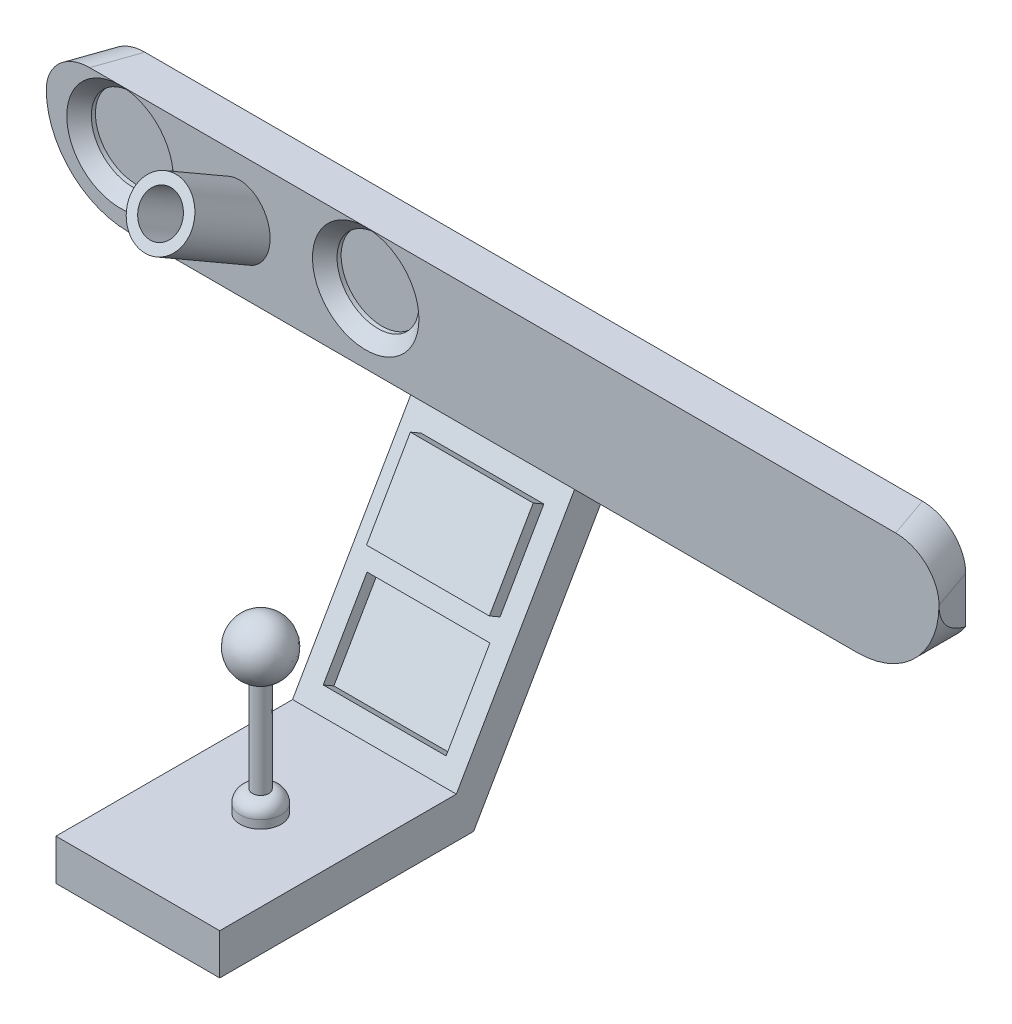
SolidWorks part; units mm, degrees
ref_plane "Front Plane" through (0, 0, 0) normal (0, 0, 1) x (1, 0, 0)
ref_plane "Top Plane" through (0, 0, 0) normal (0, 1, 0) x (1, 0, 0)
ref_plane "Right Plane" through (0, 0, 0) normal (1, 0, 0) x (0, 0, -1)
sketch "Sketch2" plane through (0, 0, 0) normal (0, 0, 1) x (1, 0, 0)
  line L1 (109, -15) -> (-109, -15)
  line L2 (109, -15) -> (109, 15)
  line L3 (109, 15) -> (-109, 15)
  line L4 (-109, -15) -> (-109, 15)
  line L5 (109, -15) -> (-109, 15) construction
  line L6 (109, 15) -> (-109, -15) construction
  point P0 (0, 0)
  dimension "D1" = 218
  dimension "D2" = 30
extrude "Boss-Extrude1" add sketch "Sketch2" along normal mid plane 10
fillet "Fillet1" radius 20 2 edges at (109, -15, 0) (-109, -15, 0)
sketch "Sketch3" plane through (0, 0, 5) normal (0, 0, 1) x (1, 0, 0)
  line L0 (-109, 15) -> (-109, 5) construction
  line L1 (109, 15) -> (-109, 15) construction
  circle A0 centre (-91, 2) radius 10
  circle A1 centre (-31, 2) radius 10
  point P8 (0, 0)
  dimension "D4" = 20
  dimension "D1" = 60
  dimension "D2" = 18
  dimension "D3" = 13
extrude "Cut-Extrude1" cut sketch "Sketch3" against normal blind 4 contours A0
extrude "Cut-Extrude2" cut sketch "Sketch3<3>" against normal blind 4
sketch "Sketch3<3>" plane through (0, 0, 5) normal (0, 0, 1) x (1, 0, 0) same geometry as "Sketch3"
chamfer "Chamfer1" distance 3 angle 45 2 edges at (-21, 2, 5) (-81, 2, 5)
ref_plane "Plane1" through (-61.85, 0, 0) normal (1, 0, 0) x (0, 0, -1)
sketch "Sketch5" plane through (-61.85, 0, 0) normal (1, 0, 0) x (0, 0, -1)
  line L0 (-20.4987, 18.4952) -> (-24.2487, 12)
  line L1 (-20.4987, 18.4952) -> (14.1423, -1.5048)
  line L2 (-24.2487, 12) -> (10.3923, -8)
  line L3 (14.1423, -1.5048) -> (10.3923, -8)
  line L4 (-5, 5) -> (-5, -15) construction
  line L5 (5, -15) -> (-5, -15) construction
  point P0 (0, -2)
  point P3 (-19.8988, -5.366)
  point P6 (0, 0)
  dimension "D1" = 40
  dimension "D2" = 7.5
  dimension "D3" = 28
  dimension "D4" = 120
  dimension "D5" = 13
revolve "Revolve1" add sketch "Sketch5" angle 360 about L2
sketch "Sketch6" plane through (0, 13.5, 23.3827) normal (0, 0.5, 0.866) x (1, 0, 0)
  circle A0 centre (-61.85, -1.7321) radius 5
  dimension "D1" = 10
extrude "Cut-Extrude3" cut sketch "Sketch6" against normal through all
sketch "Sketch7" plane through (0, 0, 0) normal (1, 0, 0) x (0, 0, -1)
  line L0 (5, -15) -> (-5, -15) construction
  line L1 (5, -15) -> (-5, -15)
  line L2 (5, -15) -> (-29.641, -75)
  line L3 (-29.641, -75) -> (-91.641, -75)
  line L4 (-5, 15) -> (5, 15) construction
  line L5 (-5, -15) -> (-33.8675, -65)
  line L6 (-33.8675, -65) -> (-91.641, -65)
  line L7 (-91.641, -65) -> (-91.641, -75)
  dimension "D1" = 90
  dimension "D2" = 120
  dimension "D3" = 62
  dimension "D4" = 10
extrude "Boss-Extrude2" add sketch "Sketch7" along normal mid plane 40
sketch "Sketch8" plane through (0, -1.5849, -2.7452) normal (0, 0.5, 0.866) x (1, 0, 0)
  line L0 (20, -15.4904) -> (20, -73.2254) construction
  line L1 (15, -20.4904) -> (-15, -20.4904)
  line L2 (15, -20.4904) -> (15, -41.8904)
  line L3 (15, -41.8904) -> (-15, -41.8904)
  line L4 (-15, -20.4904) -> (-15, -41.8904)
  line L5 (15, -20.4904) -> (-15, -41.8904) construction
  line L6 (15, -41.8904) -> (-15, -20.4904) construction
  line L7 (15, -46.8254) -> (-15, -46.8254)
  line L8 (15, -46.8254) -> (15, -68.2254)
  line L9 (15, -68.2254) -> (-15, -68.2254)
  line L10 (-15, -46.8254) -> (-15, -68.2254)
  line L11 (15, -46.8254) -> (-15, -68.2254) construction
  line L12 (15, -68.2254) -> (-15, -46.8254) construction
  line L13 (-20, -15.4904) -> (-20, -73.2254) construction
  line L14 (-89, -15.4904) -> (-20, -15.4904) construction
  line L15 (20, -73.2254) -> (-20, -73.2254) construction
  point P0 (0, -31.1904)
  point P5 (0, -57.5254)
  dimension "D1" = 5
  dimension "D2" = 5
  dimension "D3" = 5
  dimension "D4" = 21.4
  dimension "D5" = 5
  dimension "D6" = 21.4
extrude "Boss-Extrude3" add sketch "Sketch8" along normal blind 3 contours L1 L4 L3 L2
sketch "Sketch10" plane through (0, -1.5849, -2.7452) normal (0, 0.5, 0.866) x (1, 0, 0)
  line L0 (20, -73.2254) -> (-20, -73.2254) construction
  line L1 (15, -68.2254) -> (-15, -68.2254)
  line L2 (15, -68.2254) -> (15, -46.8254)
  line L3 (15, -46.8254) -> (-15, -46.8254)
  line L4 (-15, -68.2254) -> (-15, -46.8254)
  line L5 (15, -68.2254) -> (-15, -46.8254) construction
  line L6 (15, -46.8254) -> (-15, -68.2254) construction
  line L7 (-20, -15.4904) -> (-20, -73.2254) construction
  point P0 (0, -57.5254)
  point P7 (-15, -57.5254)
  point P12 (0, 0)
  dimension "D1" = 5
  dimension "D2" = 5
  dimension "D4" = 21.4
extrude "Cut-Extrude4" cut sketch "Sketch10" against normal blind 3
sketch "Sketch11" plane through (0, 0, 0) normal (1, 0, 0) x (0, 0, -1)
  line L0 (-61.641, -23.0812) -> (-61.641, -85)
  line L1 (-61.641, -85) -> (-54.141, -85)
  line L2 (-54.141, -85) -> (-54.141, -75)
  line L3 (-91.641, -75) -> (-29.641, -75) construction
  line L4 (-54.141, -75) -> (-56.641, -75)
  line L5 (-56.641, -75) -> (-56.641, -63)
  line L6 (-59.641, -60) -> (-59.641, -36.5846)
  line L7 (-91.641, -65) -> (-91.641, -75) construction
  line L8 (-33.8675, -65) -> (-91.641, -65) construction
  arc A0 (-56.641, -63) -> (-59.641, -60) centre (-59.641, -63) ccw
  arc A1 (-61.641, -23.0812) -> (-59.641, -36.5846) centre (-61.7693, -30) cw
  point P14 (-91.641, -70)
  point P17 (0, 0)
  point P18 (-61.641, -30)
  point P19 (-59.641, -36.5846)
  dimension "D6" = 3
  dimension "D9" = 6.92
  dimension "D1" = 30
  dimension "D2" = 7.5
  dimension "D3" = 5
  dimension "D4" = 10
  dimension "D5" = 2
  dimension "D7" = 2
  dimension "D8" = 35
revolve "Revolve2" add sketch "Sketch11" angle 360 about L0
sketch "Sketch12" plane through (0, 15, 0) normal (0, 1, 0) x (1, 0, 0)
  line L0 (-109, -5) -> (-109, 5)
  line L1 (-109, 5) -> (-105.52, 5)
  line L2 (109, 5) -> (-109, 5) construction
  line L3 (-105.52, 5) -> (-109, -5)
  dimension "D1" = 3.48
extrude "Cut-Extrude5" cut sketch "Sketch12" against normal blind 40
fillet "Fillet2" radius 10 1 edges at (-107.26, 15, 0)
mirror "Mirror1" about plane through (0, 0, 0) normal (1, 0, 0) of "Fillet2", "Cut-Extrude5"
